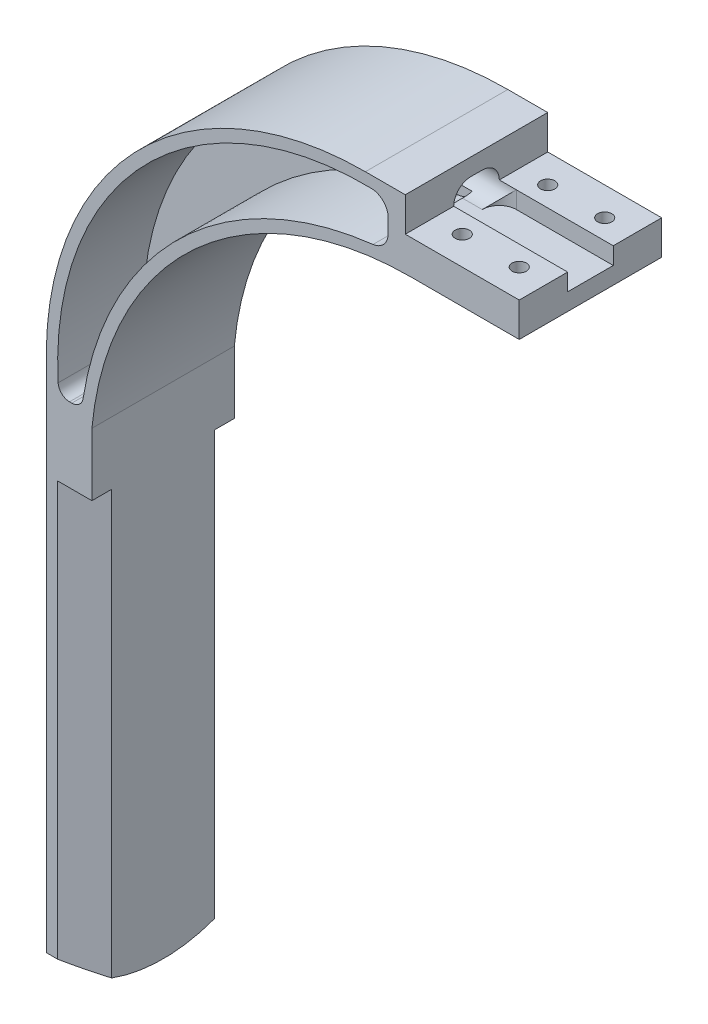
SolidWorks part; units mm, degrees
material "Сплав 2024"
ref_plane "Спереди" through (0, 0, 0) normal (0, 0, 1) x (1, 0, 0)
ref_plane "Сверху" through (0, 0, 0) normal (0, 1, 0) x (1, 0, 0)
ref_plane "Справа" through (0, 0, 0) normal (1, 0, 0) x (0, 0, -1)
sketch "Эскиз1" plane through (0, 0, 0) normal (0, 0, 1) x (1, 0, 0)
  line L0 (0, 0) -> (0, 95)
  line L1 (0, 0) -> (8, 0)
  line L2 (-20.7345, 150) -> (144.5665, 150) construction
  line L3 (83, 163.3115) -> (83, 122.0175) construction
  line L4 (8, 0) -> (8, 87)
  line L6 (83, 150) -> (56, 150)
  line L7 (83, 150) -> (83, 138)
  line L8 (83, 138) -> (64, 138)
  arc A0 (64, 138) -> (8, 87) centre (64, 81.7549) ccw
  arc A1 (56, 150) -> (0, 95) centre (56, 93.9909) ccw
  dimension "D1" = 95
  dimension "D2" = 87
  dimension "D3" = 150
  dimension "D4" = 83
  dimension "D5" = 8
  dimension "D6" = 12
  dimension "D7" = 27
  dimension "D8" = 19
extrude "Бобышка-Вытянуть1" add sketch "Эскиз1" along normal blind 25
sketch "Эскиз2" plane through (0, 0, 25) normal (0, 0, 1) x (1, 0, 0)
  line L1 (83, 150) -> (63, 150)
  line L2 (83, 150) -> (83, 144)
  line L3 (83, 144) -> (63, 144)
  line L4 (63, 150) -> (63, 144)
  dimension "D1" = 20
  dimension "D2" = 6
extrude "Вырез-Вытянуть1" cut sketch "Эскиз2" against normal through all
sketch "Эскиз5" plane through (0, 0, 0) normal (0, -1, 0) x (1, 0, 0)
  line L0 (8, 3.4641) -> (2, 0)
  line L1 (8, 25) -> (8, 0) construction
  line L3 (2, 0) -> (8, 0)
  line L4 (8, 0) -> (8, 3.4641)
  line L5 (0, 25) -> (0, 0) construction
  line L6 (8, 12.5) -> (7.5, 12.5) construction
  line L7 (8, 25) -> (8, 0) construction
  line L8 (8, 25) -> (8, 21.5359)
  line L9 (2, 25) -> (8, 25)
  line L10 (8, 21.5359) -> (2, 25)
  line L11 (0, 0) -> (8, 0) construction
  dimension "D1" = 2
  dimension "D2" = 60
extrude "Вырез-Вытянуть2" cut sketch "Эскиз5" against normal blind 76
sketch "Эскиз6" plane through (0, 0, 0) normal (-1, 0, 0) x (0, 0, 1)
  line L0 (12.5, 0) -> (12.5, 16.6862) construction
  line L1 (25, 0) -> (0, 0) construction
  line L2 (12.5, -11.9161) -> (12.5, 92.5) construction
  line L3 (10, -11.9161) -> (10, 92.5)
  line L4 (15, -11.9161) -> (15, 92.5)
  line L5 (25, 95) -> (0, 95) construction
  arc A0 (10, -11.9161) -> (15, -11.9161) centre (12.5, -11.9161) ccw
  arc A1 (15, 92.5) -> (10, 92.5) centre (12.5, 92.5) ccw
  point P7 (12.5, 40.292)
  dimension "D1" = 5
extrude "Вырез-Вытянуть4" cut sketch "Эскиз6" against normal blind 5
sketch "Эскиз3" plane through (0, 0, 25) normal (0, 0, -1) x (-1, 0, 0)
  line L0 (-60, 147.8517) -> (-60, 139.8625)
  line L1 (-63, 150) -> (-63, 144) construction
  line L2 (-6.2158, 89.0676) -> (-2.2158, 89.0676)
  arc A4 (-60, 147.8517) -> (-2.2158, 89.0676) centre (-56, 93.9909) cw
  arc A5 (-60, 139.8625) -> (-6.2158, 89.0676) centre (-64, 81.7549) cw
  arc A6 (0, 95) -> (-56, 150) centre (-56, 93.9909) ccw construction
  arc A7 (-8, 87) -> (-64, 138) centre (-64, 81.7549) ccw construction
  dimension "D1" = 2
  dimension "D2" = 2
  dimension "D3" = 3
  dimension "D4" = 4
extrude "Вырез-Вытянуть3" cut sketch "Эскиз3" along normal up to surface (15 mm away) up to face at (2.5, 46.25, 10)
fillet "Скругление3" radius 2 2 edges at (6.2158, 89.0676, 17.5) (2.2158, 89.0676, 20)
fillet "Скругление4" radius 3 2 edges at (60, 147.8517, 17.5) (60, 139.8625, 17.5)
ref_plane "Плоскость1" through (0, 10, 0) normal (0, 1, 0) x (1, 0, 0)
sketch "Эскиз8" plane through (0, 10, 0) normal (0, 1, 0) x (1, 0, 0)
  line L0 (0, -2) -> (1.5, -2)
  line L1 (0, -12.5) -> (0, 0) construction
  line L2 (1.5, -2) -> (1.5, -3)
  line L3 (3.5, -4) -> (5.5, -4)
  line L4 (5.5, -4) -> (5.5, -8)
  line L5 (5.5, -8) -> (0, -8)
  line L6 (0, -8) -> (0, -2)
  line L7 (56, 0) -> (0, 0) construction
  line L8 (2.0115, -10) -> (0, -10) construction
  line L9 (1.5, -3) -> (3.5, -3)
  line L10 (3.5, -3) -> (3.5, -4)
  line L11 (8, -25) -> (8, 0) construction
  line L12 (8, -12.5) -> (6.1534, -12.5) construction
  line L13 (3.5, -22) -> (3.5, -21)
  line L14 (1.5, -22) -> (3.5, -22)
  line L15 (0, -17) -> (0, -23)
  line L16 (5.5, -17) -> (0, -17)
  line L17 (5.5, -21) -> (5.5, -17)
  line L18 (3.5, -21) -> (5.5, -21)
  line L19 (1.5, -23) -> (1.5, -22)
  line L20 (0, -23) -> (1.5, -23)
  dimension "D1" = 2
  dimension "D2" = 2
  dimension "D3" = 4
  dimension "D4" = 1
  dimension "D5" = 1.5
  dimension "D6" = 2
  dimension "D7" = 2.5
extrude "Вырез-Вытянуть6" cut sketch "Эскиз8" along normal blind 75
sketch "Эскиз9" plane through (0, 144, 0) normal (0, 1, 0) x (1, 0, 0)
  line L0 (83, 0) -> (63, -25) construction
  line L1 (83, 0) -> (83, -25) construction
  line L2 (68, -5) -> (78, -5) construction
  line L3 (68, -5) -> (68, -20) construction
  line L4 (68, -20) -> (78, -20) construction
  line L5 (78, -5) -> (78, -20) construction
  line L6 (68, -5) -> (78, -20) construction
  line L7 (68, -20) -> (78, -5) construction
  line L8 (63, 0) -> (83, 0) construction
  line L9 (63, 0) -> (63, -25) construction
  point P4 (73, -12.5)
  dimension "D1" = 5
  dimension "D2" = 5
hole_wizard "Отверстие обработанное метчиком M3x0.51" positions "Эскиз11" profile "Эскиз10" tap size "M3x0.5" standard "Ansi Metric" end condition up to next
sketch "Эскиз11" plane through (19.192, 144, 18.7997) normal (0, 1, 0) x (1, 0, 0)
  point P0 (48.808, 13.7997)
  point P3 (58.808, 13.7997)
  point P6 (58.808, -1.2003)
  point P9 (48.808, -1.2003)
sketch "Эскиз10" plane through (68, 144, 5) normal (1, 0, 0) x (0, 0, 1)
  line L0 (0, 0) -> (0, 6)
  line L1 (0, 6) -> (1.25, 6)
  line L2 (1.25, 6) -> (1.25, 0)
  line L5 (1.25, 0) -> (0, 0)
  line L11 (0, -6.35) -> (0, 107.95) construction
  dimension "Диаметр резьбы" = 2.5
  dimension "Глубина проходного сверла" = 6
sketch "Эскиз12" plane through (0, 0, 0) normal (-1, 0, 0) x (0, 0, 1)
  line L0 (12.5, 0) -> (12.5, 6.3491) construction
  line L1 (10, 0) -> (15, 0) construction
  line L3 (0, 3.302) -> (0, 0)
  line L4 (0, 95) -> (0, 0) construction
  line L5 (0, 0) -> (12.5, 0)
  line L6 (12.5, 0) -> (25, 0)
  line L7 (25, 0) -> (25, 3.302)
  line L8 (25, 95) -> (25, 0) construction
  arc A0 (0, 3.302) -> (25, 3.302) centre (12.5, 26.1) ccw
  dimension "D1" = 52
  dimension "D2" = 26.1
extrude "Вырез-Вытянуть7" cut sketch "Эскиз12" against normal up to next
sketch "Эскиз13" plane through (0, 144, 0) normal (0, 1, 0) x (1, 0, 0)
  line L0 (83, -12.5) -> (63, -12.5) construction
  line L1 (83, 0) -> (83, -25) construction
  line L2 (63, 0) -> (63, -25) construction
  line L4 (63, -8.5) -> (83, -8.5)
  line L5 (63, -8.5) -> (63, -16.5)
  line L6 (63, -16.5) -> (83, -16.5)
  line L7 (83, -8.5) -> (83, -16.5)
  line L8 (63, -8.5) -> (83, -16.5) construction
  line L9 (63, -16.5) -> (83, -8.5) construction
  point P6 (73, -12.5)
  dimension "D1" = 8
extrude "Вырез-Вытянуть8" cut sketch "Эскиз13" against normal blind 3
fillet "Скругление8" radius 3 2 edges at (63, 142.5, 8.5) (63, 142.5, 16.5)
sketch "Эскиз14" plane through (83, 0, 0) normal (1, 0, 0) x (0, 0, -1)
  line L0 (-12.5, 141) -> (-12.5, 154.1514) construction
  line L1 (-16.5, 141) -> (-8.5, 141) construction
  line L4 (-13.5, 144) -> (-11.5, 144) construction
  line L5 (-13.5, 147) -> (-11.5, 147)
  line L6 (-13.5, 141) -> (-11.5, 141)
  line L7 (-16.5, 141) -> (-16.5, 144) construction
  arc A0 (-13.5, 147) -> (-13.5, 141) centre (-13.5, 144) ccw
  arc A1 (-11.5, 141) -> (-11.5, 147) centre (-11.5, 144) ccw
  point P5 (-12.5, 144)
  dimension "D1" = 6
extrude "Вырез-Вытянуть9" cut sketch "Эскиз14" against normal blind 28
sketch "Эскиз15" plane through (0, 0, 0) normal (-1, 0, 0) x (0, 0, 1)
  line L0 (12.5, 92.5) -> (12.5, 85.5) construction
  line L1 (15, 92.5) -> (15, 85.5)
  line L2 (10, 92.5) -> (10, 85.5)
  line L3 (15, 0.2205) -> (15, 89.1366) construction
  arc A0 (15, 92.5) -> (10, 92.5) centre (12.5, 92.5) ccw
  arc A1 (10, 85.5) -> (15, 85.5) centre (12.5, 85.5) ccw
  point P3 (12.5, 89)
  dimension "D1" = 7
extrude "Вырез-Вытянуть10" cut sketch "Эскиз15" against normal blind 6
sketch "Эскиз19" plane through (0, 0, 0) normal (-1, 0, 0) x (0, 0, 1)
  line L0 (10, 85.5) -> (10, 0.2205) construction
  line L1 (15, 92.5) -> (15, 0.2205) construction
  line L2 (10, 10.1) -> (10, 0.2205)
  line L3 (15, 10.1) -> (15, 0.2205)
  line L4 (10, 10.1) -> (15, 10.1)
  arc A0 (10, 0.2205) -> (15, 0.2205) centre (12.5, 26.1) ccw construction
  arc A1 (10, 0.2205) -> (15, 0.2205) centre (12.5, 26.1) ccw
  dimension "D1" = 16
extrude "Бобышка-Вытянуть2" add sketch "Эскиз19" against normal up to surface (5 mm away) up to face at (5, 42.2051, 12.5)
sketch "Эскиз16" plane through (0, 0, 0) normal (-1, 0, 0) x (0, 0, 1)
  line L0 (25, 5.1) -> (0, 5.1) construction
  line L1 (25, 95) -> (25, 3.302) construction
  line L3 (0, 95) -> (0, 3.302) construction
  arc A0 (0, 3.302) -> (25, 3.302) centre (12.5, 26.1) ccw construction
  point P4 (12.5, 0.1)
  dimension "D1" = 5
hole_wizard "Отверстие обработанное метчиком M3x0.52" positions "Эскиз18" profile "Эскиз17" tap size "M3x0.5" standard "Ansi Metric"
sketch "Эскиз18" plane through (0, 0, 0) normal (-1, 0, 0) x (0, 0, 1)
  line L1 (25, 5.1) -> (0, 5.1) construction
  point P5 (12.5, 5.1)
sketch "Эскиз17" plane through (0, 5.1, 12.5) normal (0, 1, 0) x (0, 0, 1)
  line L0 (0, 0) -> (0, 4.7511)
  line L1 (0, 4.7511) -> (1.25, 4)
  line L2 (1.25, 4) -> (1.25, 0)
  line L5 (1.25, 0) -> (0, 0)
  line L10 (0, 4.7511) -> (-1.25, 4) construction
  line L11 (0, -6.35) -> (0, 107.95) construction
  dimension "Диаметр сверла" = 2.5
  dimension "Глубина сверла" = 4
  dimension "Угол заточки сверла" = 118
cosmetic thread "Отверстие резьбы1" parameters "D1"=4, "D2"=3
